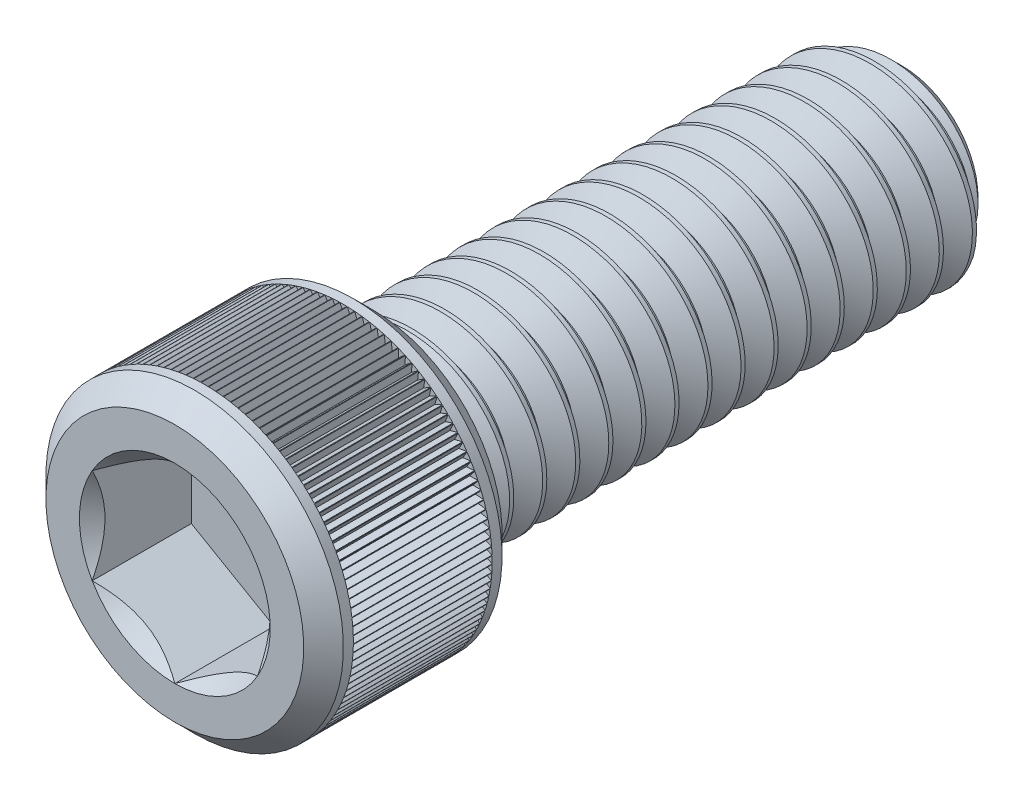
SolidWorks part; units mm, degrees
ref_plane "Front Plane" through (0, 0, 0) normal (0, 0, 1) x (1, 0, 0)
ref_plane "Top Plane" through (0, 0, 0) normal (0, 1, 0) x (1, 0, 0)
ref_plane "Right Plane" through (0, 0, 0) normal (1, 0, 0) x (0, 0, -1)
sketch "Sketch1" plane through (0, 0, 0) normal (1, 0, 0) x (0, 0, -1)
  line L0 (17.4625, 0) -> (-17.4625, 0) construction
  line L1 (-17.4625, 0) -> (-17.4625, 6.1912)
  line L2 (-17.4625, 6.1912) -> (-16.51, 7.1437)
  line L3 (-16.51, 7.1437) -> (-8.89, 7.1437)
  line L4 (-8.89, 7.1437) -> (-7.9375, 6.1912)
  line L5 (-7.9375, 6.1912) -> (-7.9375, 4.7625)
  line L6 (-7.9375, 4.7625) -> (16.3513, 4.7625)
  line L7 (16.3513, 4.7625) -> (17.4625, 3.6513)
  line L8 (17.4625, 3.6513) -> (17.4625, 0)
  line L9 (17.3633, 4.9344) -> (18.9508, 4.9344) construction
  line L10 (18.9508, 4.9344) -> (18.157, 3.5595) construction
  line L11 (18.157, 3.5595) -> (17.3633, 4.9344) construction
  line L12 (17.4625, 4.7625) -> (18.8516, 4.7625) construction
  line L13 (18.157, 4.9344) -> (18.157, 4.7625) construction
  line L14 (18.0578, 3.7314) -> (18.2563, 3.7314) construction
  line L15 (18.157, 3.7314) -> (18.157, 3.5595) construction
  line L16 (17.4129, 4.8484) -> (18.9012, 4.8484)
  line L17 (18.9012, 4.8484) -> (18.2563, 3.7314)
  line L18 (18.2563, 3.7314) -> (18.0578, 3.7314)
  line L19 (18.0578, 3.7314) -> (17.4129, 4.8484)
  line L20 (16.3513, -4.7625) -> (13.4938, -4.7625) construction
  point P3 (-16.0338, 7.1437)
  point P4 (0, 0)
  point P25 (18.157, 4.8484)
  point P26 (17.4625, 4.7625)
  point P28 (-9.3662, 7.1437)
  point P29 (-12.7, 7.1437)
  point P33 (13.4938, -4.7625)
  dimension "Head Ht" = 9.525
  dimension "Screw Size" = 9.525
  dimension "Head Dia" = 14.2875
  dimension "D1" = 45
  dimension "D2" = 45
  dimension "D3" = 0.9525
  dimension "D4" = 0.9525
  dimension "Pitch" = 1.5875
  dimension "D5" = 0.1984
  dimension "D6" = 1.1113
  dimension "D7" = 2.8575
  dimension "Length" = 25.4
  dimension "D8" = 0.4762
  dimension "D9" = 0.4762
sketch "Sketch2" plane through (0, 0, 0) normal (0, 0, 1) x (1, 0, 0)
  line L0 (-0.1657, 7.1418) -> (0, 6.7866)
  line L1 (0, 4.5827) -> (-3.9688, 2.2914)
  line L2 (-3.9688, 2.2914) -> (-3.9687, -2.2914)
  line L3 (-3.9687, -2.2914) -> (0, -4.5827)
  line L4 (0, -4.5827) -> (3.9688, -2.2914)
  line L5 (3.9688, -2.2914) -> (3.9688, 2.2914)
  line L6 (3.9688, 2.2914) -> (0, 4.5827)
  line L7 (0, 6.7866) -> (0.1657, 7.1418)
  line L8 (0, -7.1437) -> (0, 7.1437) construction
  line L9 (0, 0) -> (0.1657, 7.1418) construction
  line L10 (0, 0) -> (-0.1657, 7.1418) construction
  circle A0 centre (0, 0) radius 3.9688 construction
  circle A1 centre (0, 0) radius 7.1437
  circle A2 centre (0, 0) radius 6.7866 construction
  point P1 (0, 7.1437)
  point P19 (0, 0)
  dimension "D1" = 14.2875
  dimension "D3" = 13.5731
  dimension "Drive Size" = 7.9375
  dimension "D2" = 2.658
sketch "Sketch3" plane through (0, 0, 0) normal (1, 0, 0) x (0, 0, -1)
  line L0 (17.4625, 0) -> (-17.4625, 0) construction
  line L1 (-17.4625, 0) -> (-17.4625, 6.1912) construction
  line L2 (-17.4625, 6.1912) -> (-16.51, 7.1437) construction
  line L3 (-16.51, 7.1437) -> (-8.89, 7.1437) construction
  line L4 (-8.89, 7.1437) -> (-7.9375, 6.1912) construction
  line L5 (-7.9375, 6.1912) -> (-7.9375, 4.7625) construction
  line L6 (-7.9375, 4.7625) -> (16.3513, 4.7625) construction
  line L7 (16.3513, 4.7625) -> (17.4625, 3.6513) construction
  line L8 (17.4625, 3.6513) -> (17.4625, 0) construction
  line L9 (17.4625, 0) -> (-17.4625, 0)
  line L10 (-17.4625, 0) -> (-17.4625, 6.1912)
  line L11 (-17.4625, 6.1912) -> (-16.51, 7.1437)
  line L12 (-16.51, 7.1437) -> (-8.89, 7.1437)
  line L13 (-8.89, 7.1437) -> (-7.9375, 6.1912)
  line L14 (-7.9375, 6.1912) -> (-7.9375, 4.7625)
  line L15 (-7.9375, 4.7625) -> (16.3513, 4.7625)
  line L16 (16.3513, 4.7625) -> (17.4625, 3.6513)
  line L17 (17.4625, 3.6513) -> (17.4625, 0)
revolve "Revolve1" add sketch "Sketch3" angle 360 about L0
sketch "Sketch4" plane through (0, 0, 17.4625) normal (0, 0, 1) x (1, 0, 0)
  line L0 (0, -4.5827) -> (3.9688, -2.2914) construction
  line L1 (3.9688, -2.2914) -> (3.9688, 2.2914) construction
  line L2 (3.9688, 2.2914) -> (0, 4.5827) construction
  line L3 (0, 4.5827) -> (-3.9688, 2.2914) construction
  line L4 (-3.9688, 2.2914) -> (-3.9687, -2.2914) construction
  line L5 (-3.9687, -2.2914) -> (0, -4.5827) construction
  line L6 (0, -4.5827) -> (3.9688, -2.2914)
  line L7 (3.9688, -2.2914) -> (3.9688, 2.2914)
  line L8 (3.9688, 2.2914) -> (0, 4.5827)
  line L9 (0, 4.5827) -> (-3.9688, 2.2914)
  line L10 (-3.9688, 2.2914) -> (-3.9687, -2.2914)
  line L11 (-3.9687, -2.2914) -> (0, -4.5827)
extrude "Cut-Extrude1" cut sketch "Sketch4" against normal blind 4.7625
sketch "Sketch5" plane through (0, 0, 17.4625) normal (0, 0, 1) x (1, 0, 0)
  circle A0 centre (0, 0) radius 4.5827
extrude "Cut-Extrude3" cut sketch "Sketch5" against normal through all draft 45
ref_axis "Center Axis1" through (0, 0, 7.9375) along (0, 0, -1)
split "Split1" bodies to split 107 resulting bodies 108 109 split by face at (0, 6.1912, 7.9375)
sketch "Sketch6" plane through (0, 0, -17.4625) normal (0, 0, -1) x (-1, 0, 0)
  circle A0 centre (0, 0) radius 4.7625 construction
  circle A1 centre (0, 0) radius 4.7625
curve "Helix/Spiral1" pitch 1.5875 height 26.9875 radius 4.7625 centre (0, 0, -17.4625) axis (0, 0, 1) start towards (0, 1, 0)
sketch "Sketch7" plane through (0, 0, 0) normal (1, 0, 0) x (0, 0, -1)
  line L0 (17.4129, 4.8484) -> (18.9012, 4.8484) construction
  line L1 (18.9012, 4.8484) -> (18.2563, 3.7314) construction
  line L2 (18.2563, 3.7314) -> (18.0578, 3.7314) construction
  line L3 (18.0578, 3.7314) -> (17.4129, 4.8484) construction
  line L4 (17.4129, 4.8484) -> (18.9012, 4.8484)
  line L5 (18.9012, 4.8484) -> (18.2563, 3.7314)
  line L6 (18.2563, 3.7314) -> (18.0578, 3.7314)
  line L7 (18.0578, 3.7314) -> (17.4129, 4.8484)
sweep "Cut-Sweep1" cut profiles "Sketch7" path "Helix/Spiral1" align with end faces yes
sketch "Sketch8" plane through (0, 0, 7.9375) normal (0, 0, -1) x (-1, 0, 0)
  circle A0 centre (0, 0) radius 4.7625
  point P3 (0, 4.7625)
extrude "Boss-Extrude1" add sketch "Sketch8" along normal blind 2.54 draft 80
ref_plane "Plane1" through (0, 0, 12.7) normal (0, 0, 1) x (1, 0, 0)
sketch "Sketch9" plane through (0, 0, 12.7) normal (0, 0, 1) x (1, 0, 0)
  line L0 (-0.1657, 7.1418) -> (0, 6.7866) construction
  line L1 (0, 6.7866) -> (0.1657, 7.1418) construction
  line L2 (-0.1657, 7.1418) -> (0, 6.7866)
  line L3 (0, 6.7866) -> (0.1657, 7.1418)
  circle A0 centre (0, 0) radius 7.1437 construction
  arc A1 (0.1657, 7.1418) -> (-0.1657, 7.1418) centre (0, 0) ccw
extrude "Cut-Extrude4" cut sketch "Sketch9" against normal up to vertex (3.3338 mm away) and the other way up to vertex (3.3338 mm away) up to point (0, 7.1437, 9.3662) other way up to point (0, 7.1437, 16.0338)
pattern_circular "CirPattern1" count 125 over 360 about axis through (0, 0, -17.4625) along (0, 0, 1) of "Cut-Extrude4" reverse direction yes
equation "\"D3@Sketch1\"=\"Head Ht@Sketch1\"/10"
equation "\"D4@Sketch1\"=\"Head Ht@Sketch1\"/10"
equation "\"D5@Sketch1\"=\"Pitch@Sketch1\"/8"
equation "\"D6@Sketch1\"=\"Pitch@Sketch1\"*.7"
equation "\"D7@Sketch1\"=\"Pitch@Sketch1\"*2.5-\"D6@Sketch1\""
equation "\"D1@Cut-Extrude1\"=\"Head Ht@Sketch1\"/2"
equation "\"D4@Helix/Spiral1\"=\"Pitch@Sketch1\""
equation "\"D3@Helix/Spiral1\"=\"Length@Sketch1\"+\"D4@Helix/Spiral1\""
equation "\"D3@Sketch2\"= \"D1@Sketch2\" * .95"
equation "\"D8@Sketch1\"=\"D4@Sketch1\"/2"
equation "\"D9@Sketch1\"=\"D3@Sketch1\"/2"
equation "\"D1@CirPattern1\"=(360/\"D2@Sketch2\")-10"
